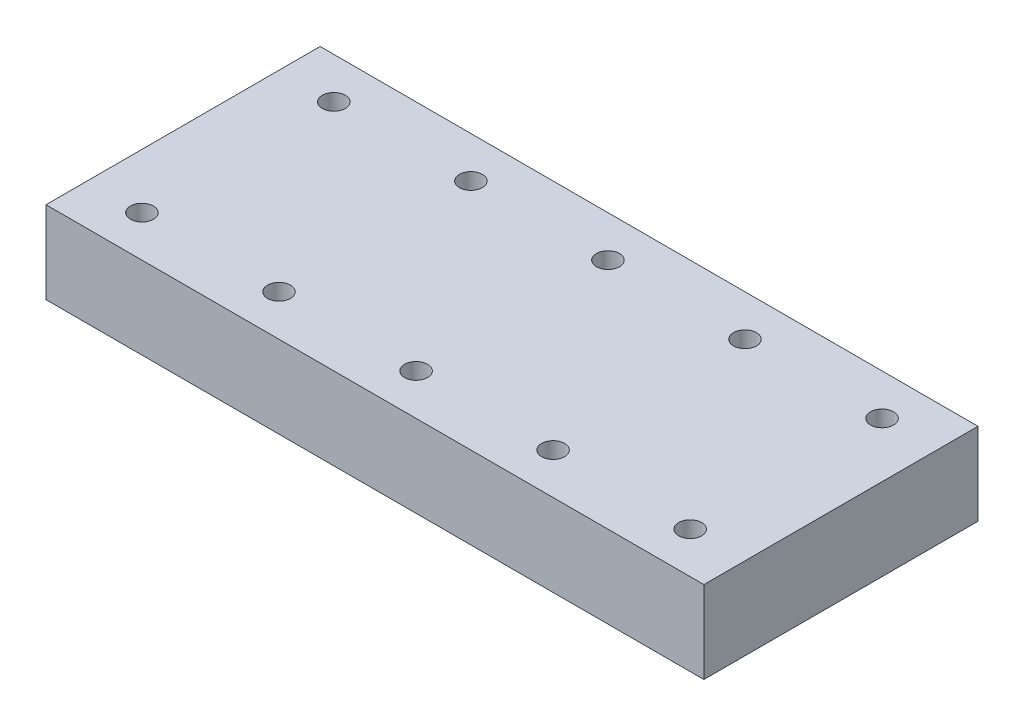
SolidWorks part; units mm, degrees
ref_plane "Front Plane" through (0, 0, 0) normal (0, 0, 1) x (1, 0, 0)
ref_plane "Top Plane" through (0, 0, 0) normal (0, 1, 0) x (1, 0, 0)
ref_plane "Right Plane" through (0, 0, 0) normal (1, 0, 0) x (0, 0, -1)
sketch "Sketch2" plane through (0, 0, 0) normal (0, 1, 0) x (1, 0, 0)
  line L0 (-46.8981, 34.5466) -> (-46.8981, -15.4534)
  line L1 (-46.8981, -15.4534) -> (73.1019, -15.4534)
  line L2 (73.1019, -15.4534) -> (73.1019, 34.5466)
  line L3 (73.1019, 34.5466) -> (-46.8981, 34.5466)
  dimension "D1" = 120
  dimension "D2" = 50
extrude "Boss-Extrude1" add sketch "Sketch2" along normal blind 15
sketch "Sketch3" plane through (0, 0, 0) normal (0, 1, 0) x (1, 0, 0)
  line L0 (74.3548, 9.5466) -> (-56.2815, 9.5466) construction
  line L1 (63.1019, 9.5466) -> (63.1019, 17.0466)
  line L2 (63.1019, 17.0466) -> (3.1019, 17.0466)
  line L3 (3.1019, 17.0466) -> (3.1019, 19.5466)
  line L4 (3.1019, 19.5466) -> (-36.8981, 19.5466)
  line L5 (-36.8981, 19.5466) -> (-36.8981, 9.5466)
  line L6 (-36.8981, 9.5466) -> (63.1019, 9.5466)
  line L7 (73.1019, -15.4534) -> (73.1019, 34.5466) construction
  line L9 (-46.8981, -15.4534) -> (73.1019, -15.4534) construction
  dimension "D1" = 60
  dimension "D2" = 40
  dimension "D3" = 10
  dimension "D4" = 25
  dimension "D5" = 10
  dimension "D6" = 7.5
sketch "Skizze7" plane through (-46.8981, 0, 0) normal (-1, 0, 0) x (0, 0, 1)
  line L1 (-34.5466, 0) -> (15.4534, 0) construction
  line L3 (-9.5466, -6.0172) -> (-9.5466, 6.0172) construction
  line L4 (15.4534, 15) -> (15.4534, 0) construction
  line L5 (-34.5466, 15) -> (-34.5466, 0) construction
  circle A0 centre (-9.5466, 2.5) radius 1.5
  dimension "D1" = 3
  dimension "D2" = 2.5
extrude "Schnitt-Linear austragen6" cut sketch "Skizze7" against normal blind 10
revolve "Schnitt-Rotation1" cut sketch "Sketch3" angle 360 about L0
sketch "Skizze10" plane through (0, 0, 0) normal (0, -1, 0) x (1, 0, 0)
  line L0 (63.1019, -17.0466) -> (3.1019, -17.0466) construction
  line L1 (53.1019, -17.0466) -> (40.6019, -17.0466)
  line L2 (53.1019, -17.0466) -> (53.1019, -14.5466)
  line L3 (53.1019, -14.5466) -> (40.6019, -14.5466)
  line L4 (40.6019, -17.0466) -> (40.6019, -14.5466)
  line L5 (63.1019, -2.0466) -> (63.1019, -17.0466) construction
  line L10 (85.7448, -9.5466) -> (-66.8579, -9.5466) construction
  line L11 (-46.8981, 15.4534) -> (73.1019, 15.4534) construction
  line L12 (73.1019, -34.5466) -> (-46.8981, -34.5466) construction
  dimension "D1" = 10
  dimension "D2" = 12.5
  dimension "D5" = 2.5
revolve "Rotation3" add sketch "Skizze10" angle 180 about L10 reverse direction yes
sketch "Skizze11" plane through (0, 0, 0) normal (0, -1, 0) x (1, 0, 0)
  line L0 (40.6019, -17.0466) -> (3.1019, -17.0466) construction
  line L1 (28.1019, -17.0466) -> (15.6019, -17.0466)
  line L2 (28.1019, -17.0466) -> (28.1019, -14.5466)
  line L3 (28.1019, -14.5466) -> (15.6019, -14.5466)
  line L4 (15.6019, -17.0466) -> (15.6019, -14.5466)
  line L5 (53.1019, -14.5466) -> (40.6019, -14.5466) construction
  line L6 (40.6019, -14.5466) -> (40.6019, -17.0466) construction
  line L7 (95.0378, -9.5466) -> (-94.5432, -9.5466) construction
  line L8 (-46.8981, 15.4534) -> (73.1019, 15.4534) construction
  line L9 (73.1019, -34.5466) -> (-46.8981, -34.5466) construction
  point P10 (40.6019, -15.7966)
  dimension "D1" = 12.5
  dimension "D2" = 12.5
revolve "Rotation4" add sketch "Skizze11" angle 180 about L7 reverse direction yes
sketch "Skizze12" plane through (0, 0, 0) normal (0, -1, 0) x (1, 0, 0)
  line L0 (73.1019, 15.4534) -> (73.1019, -34.5466) construction
  line L1 (-46.8981, -34.5466) -> (-46.8981, 15.4534) construction
  line L2 (-46.8981, 15.4534) -> (73.1019, 15.4534) construction
  line L3 (-46.8981, 15.4534) -> (73.1019, 15.4534) construction
  circle A0 centre (-36.8981, 7.9534) radius 2.1
  circle A1 centre (13.1019, 7.9534) radius 2.1
  circle A2 centre (63.1019, 7.9534) radius 2.1
  circle A3 centre (38.1019, 7.9534) radius 2.1
  circle A4 centre (-11.8981, 7.9534) radius 2.1
  point P16 (0, 0)
  dimension "D3" = 4.2
  dimension "D6" = 4.2
  dimension "D7" = 4.2
  dimension "D8" = 25
  dimension "D9" = 25
  dimension "D10" = 50
  dimension "D11" = 7.5
  dimension "D2" = 10
  dimension "D4" = 10
  dimension "D5" = 7.5
  dimension "D1" = 3
ref_plane "Ebene6" through (0, 0, -9.5466) normal (0, 0, 1) x (1, 0, 0)
extrude "Schnitt-Linear austragen7" cut sketch "Skizze12" against normal through all
mirror "Spiegeln1" about plane through (0, 0, -9.5466) normal (0, 0, 1) of "Schnitt-Linear austragen7"
sketch "Skizze13" plane through (-46.8981, 0, 0) normal (-1, 0, 0) x (0, 0, 1)
  line L0 (-34.5466, 0) -> (15.4534, 0) construction
  line L1 (15.4534, 15) -> (0.4534, 15)
  line L2 (15.4534, 15) -> (15.4534, 5)
  line L3 (15.4534, 5) -> (0.4534, 5)
  line L4 (0.4534, 15) -> (0.4534, 5)
  line L5 (-34.5466, 0) -> (15.4534, 0) construction
  line L6 (-34.5466, 15) -> (-19.5466, 15)
  line L7 (-34.5466, 15) -> (-34.5466, 5)
  line L8 (-34.5466, 5) -> (-19.5466, 5)
  line L9 (-19.5466, 15) -> (-19.5466, 5)
  dimension "D1" = 15
  dimension "D2" = 5
  dimension "D3" = 15
  dimension "D4" = 5
fillet "Fillet2" radius 1 1 edges at (3.1019, 7.5, -9.5466)
fillet "Fillet3" radius 1 1 edges at (15.6019, 5, -9.5466)
fillet "Fillet4" radius 1 1 edges at (28.1019, 5, -9.5466)
fillet "Fillet5" radius 1 1 edges at (40.6019, 5, -9.5466)
fillet "Fillet6" radius 1 1 edges at (53.1019, 5, -9.5466)
